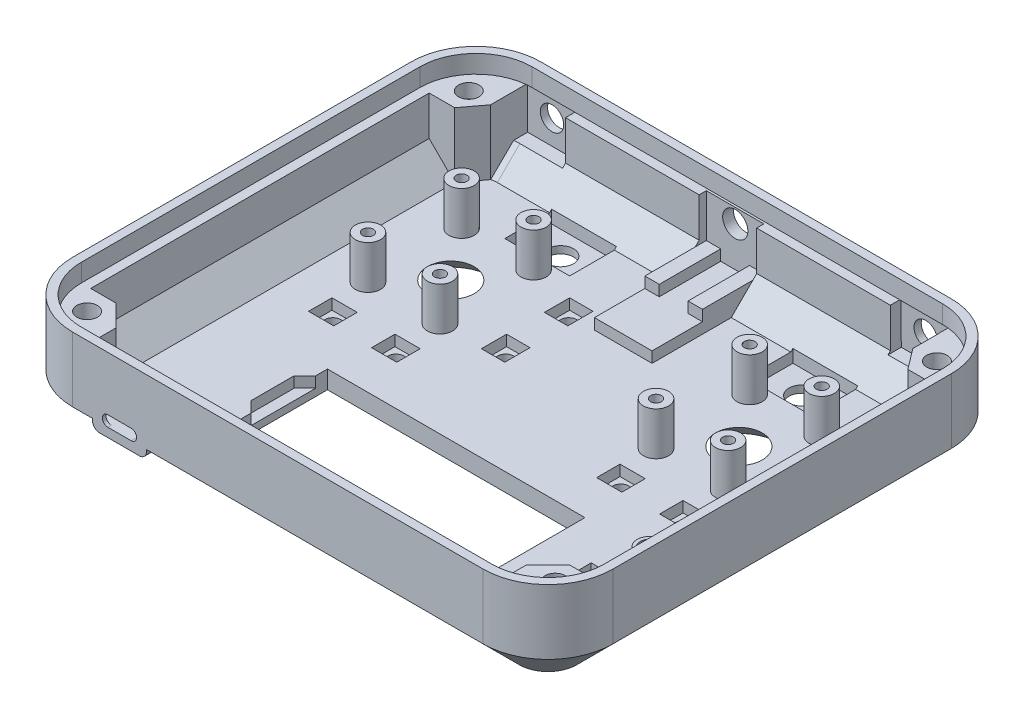
SolidWorks part; units mm, degrees
ref_plane "前视基准面" through (0, 0, 0) normal (0, 0, 1) x (1, 0, 0)
ref_plane "上视基准面" through (0, 0, 0) normal (0, 1, 0) x (1, 0, 0)
ref_plane "右视基准面" through (0, 0, 0) normal (1, 0, 0) x (0, 0, -1)
other "Configuration Table"
sketch "草图1" plane through (0, 0, 0) normal (0, 1, 0) x (1, 0, 0)
  line L1 (-57, -65) -> (57, -65)
  line L2 (-75, -47) -> (-75, 47)
  line L3 (-57, 65) -> (57, 65)
  line L4 (75, -47) -> (75, 47)
  line L5 (-75, -65) -> (75, 65) construction
  line L6 (-75, 65) -> (75, -65) construction
  arc A0 (57, -65) -> (75, -47) centre (57, -47) ccw
  arc A1 (-57, -65) -> (-75, -47) centre (-57, -47) cw
  arc A2 (-75, 47) -> (-57, 65) centre (-57, 47) cw
  arc A3 (57, 65) -> (75, 47) centre (57, 47) cw
  point P0 (0, 0)
  dimension "D3" = 18
  dimension "D1" = 150
  dimension "D2" = 130
extrude "凸台-拉伸1" add sketch "草图1" along normal blind 23
chamfer "倒角1" distance 10 angle 45 8 edges at (75, 0, 0) (69.7279, 0, -59.7279) (0, 0, -65) (-69.7279, 0, -59.7279) (-75, 0, 0) (-69.7279, 0, 59.7279) (0, 0, 65) (69.7279, 0, 59.7279)
shell "抽壳3" thickness 5 removed face at (0, 23, 0)
sketch "草图2" plane through (0, 0, -65) normal (0, 0, -1) x (-1, 0, 0)
  line L0 (0, 0) -> (0, 23) construction
  line L1 (-57, 23) -> (57, 23) construction
  circle A0 centre (0, 19) radius 3.5
  circle A1 centre (-51.8897, 18) radius 3.25
  circle A2 centre (51.8897, 18) radius 3.25
  dimension "D1" = 7
  dimension "D2" = 6.5
  dimension "D3" = 5
  dimension "D4" = 4
extrude "切除-拉伸1" cut sketch "草图2" against normal blind 27
sketch "草图3" plane through (0, 0, 0) normal (0, -1, 0) x (1, 0, 0)
  line L0 (0, 0) -> (0, -65) construction
  line L1 (57, -65) -> (-57, -65) construction
  line L2 (-57, -55) -> (57, -55) construction
  line L3 (40, -23) -> (40, 55) construction
  line L4 (57, 55) -> (-57, 55) construction
  line L5 (65, -47) -> (65, 47) construction
  line L6 (60, 25.5) -> (47.5, 25.5)
  line L7 (60, 25.5) -> (60, 45)
  line L8 (60, 45) -> (47.5, 45)
  line L9 (47.5, 25.5) -> (47.5, 45)
  line L11 (35.75, 40) -> (-35.75, 40)
  line L12 (35.75, 40) -> (35.75, 15.5)
  line L13 (35.75, 15.5) -> (-35.75, 15.5)
  line L14 (-35.75, 40) -> (-35.75, 15.5)
  line L15 (35.75, 40) -> (-35.75, 15.5) construction
  line L16 (35.75, 15.5) -> (-35.75, 40) construction
  circle A0 centre (33.5, -47) radius 3.6
  circle A1 centre (-33.5, -47) radius 3.6
  circle A2 centre (40, -23) radius 6
  circle A3 centre (-40, -23) radius 6
  circle A4 centre (48.75, 1) radius 2.25
  circle A5 centre (31.25, 1) radius 2.25
  circle A6 centre (-31.25, 1) radius 2.25
  circle A7 centre (-48.75, 1) radius 2.25
  circle A8 centre (-16, -31.75) radius 2.25
  circle A9 centre (-16, -14.25) radius 2.25
  arc A14 (-30.1535, -45.0353) -> (-30.1535, -48.9647) centre (-31.25, -47) cw [skipped]
  circle A15 centre (-48.75, -47) radius 2.25 [skipped]
  circle A16 centre (-64, -31.75) radius 2.25 [skipped]
  circle A17 centre (-64, -14.25) radius 2.25 [skipped]
  circle A18 centre (53.75, 15.5) radius 2.6
  point P38 (0, 27.75)
  point P41 (-40, -23)
  dimension "D1" = 7.2
  dimension "D2" = 67
  dimension "D3" = 8
  dimension "D5" = 80
  dimension "D6" = 12
  dimension "D7" = 4.5
  dimension "D8" = 17.5
  dimension "D9" = 24
  dimension "D15" = 5.2
  dimension "D4" = 32
  dimension "D11" = 19.5
  dimension "D12" = 12.5
  dimension "D13" = 5
  dimension "D14" = 10
  dimension "D16" = 10
  dimension "D17" = 71.5
  dimension "D18" = 24.5
  dimension "D19" = 15
  dimension "D10" = 4
extrude "切除-拉伸2" cut sketch "草图3" against normal blind 27
sketch "草图4" plane through (0, 5, 0) normal (0, 1, 0) x (1, 0, 0)
  circle A0 centre (53.75, -15.5) radius 3.5
  circle A1 centre (53.75, -15.5) radius 2.6
  dimension "D1" = 5.2
  dimension "D2" = 7
extrude "凸台-拉伸2" add sketch "草图4" along normal blind 2
sketch "草图6" plane through (0, 5, 0) normal (0, 1, 0) x (1, 0, 0)
  line L0 (0, 0) -> (0, 65) construction
  line L1 (24.5, 40.5) -> (42.5, 40.5)
  line L2 (24.5, 40.5) -> (24.5, 53.5)
  line L3 (24.5, 53.5) -> (42.5, 53.5)
  line L4 (42.5, 40.5) -> (42.5, 53.5)
  line L5 (24.5, 40.5) -> (42.5, 53.5) construction
  line L6 (24.5, 53.5) -> (42.5, 40.5) construction
  line L7 (57, 65) -> (-57, 65) construction
  line L8 (-24.5, 53.5) -> (-42.5, 53.5)
  line L9 (-42.5, 40.5) -> (-42.5, 53.5)
  line L10 (-24.5, 40.5) -> (-42.5, 40.5)
  line L11 (-24.5, 40.5) -> (-24.5, 53.5)
  point P0 (33.5, 47)
  dimension "D1" = 13
  dimension "D2" = 18
extrude "切除-拉伸3" cut sketch "草图6" against normal mid plane 6
sketch "草图7" plane through (0, 23, 0) normal (0, 1, 0) x (1, 0, 0)
  line L6 (57, 65) -> (-57, 65) construction
  line L7 (-8.0392, 52.4354) -> (7.9608, 52.4354)
  line L8 (-8.0392, 52.4354) -> (-8.0392, 62)
  line L9 (-8.0392, 62) -> (7.9608, 62)
  line L10 (7.9608, 52.4354) -> (7.9608, 62)
  line L11 (-8.0392, 52.4354) -> (7.9608, 62) construction
  line L12 (-8.0392, 62) -> (7.9608, 52.4354) construction
  point P0 (-0.0392, 57.2177)
  dimension "D1" = 16
  dimension "D2" = 3
extrude "切除-拉伸8" cut sketch "草图7" against normal blind 14
sketch "草图8" plane through (0, 0, -60) normal (0, 0, 1) x (1, 0, 0)
  line L0 (0, 0) -> (-0.0392, 23) construction
  line L1 (-58.6397, 11.25) -> (-45.1397, 11.25)
  line L2 (-58.6397, 11.25) -> (-58.6397, 24.75)
  line L3 (-58.6397, 24.75) -> (-45.1397, 24.75)
  line L4 (-45.1397, 11.25) -> (-45.1397, 24.75)
  line L5 (-58.6397, 11.25) -> (-45.1397, 24.75) construction
  line L6 (-58.6397, 24.75) -> (-45.1397, 11.25) construction
  line L7 (-57, 0) -> (57, 0) construction
  line L8 (7.9608, 23) -> (-8.0392, 23) construction
  line L9 (58.5549, 24.95) -> (45.0549, 24.9039)
  line L10 (45.101, 11.404) -> (45.0549, 24.9039)
  line L11 (58.6009, 11.4501) -> (45.101, 11.404)
  line L12 (58.6009, 11.4501) -> (58.5549, 24.95)
  point P0 (-51.8897, 18)
  dimension "D1" = 13.5
  dimension "D2" = 13.5
extrude "切除-拉伸9" cut sketch "草图8" along normal blind 13 from offset 3 offset against normal yes
sketch "草图9" plane through (0, 5, 0) normal (0, 1, 0) x (1, 0, 0)
  line L1 (-52.25, -4.25) -> (-45.25, -4.25)
  line L2 (-52.25, -4.25) -> (-52.25, 2.25)
  line L3 (-52.25, 2.25) -> (-45.25, 2.25)
  line L4 (-45.25, -4.25) -> (-45.25, 2.25)
  line L5 (-52.25, -4.25) -> (-45.25, 2.25) construction
  line L6 (-52.25, 2.25) -> (-45.25, -4.25) construction
  line L7 (-34.75, -4.25) -> (-27.75, -4.25)
  line L8 (-34.75, -4.25) -> (-34.75, 2.25)
  line L9 (-34.75, 2.25) -> (-27.75, 2.25)
  line L10 (-27.75, -4.25) -> (-27.75, 2.25)
  line L11 (-34.75, -4.25) -> (-27.75, 2.25) construction
  line L12 (-34.75, 2.25) -> (-27.75, -4.25) construction
  line L13 (0, 0) -> (0, 52.9289) construction
  line L14 (-24.5, 52.9289) -> (24.5, 52.9289) construction
  line L15 (34.75, 2.25) -> (27.75, -4.25) construction
  line L16 (34.75, -4.25) -> (27.75, 2.25) construction
  line L17 (52.25, 2.25) -> (45.25, -4.25) construction
  line L18 (52.25, -4.25) -> (45.25, 2.25) construction
  line L19 (27.75, -4.25) -> (27.75, 2.25)
  line L20 (34.75, 2.25) -> (27.75, 2.25)
  line L21 (34.75, -4.25) -> (34.75, 2.25)
  line L22 (34.75, -4.25) -> (27.75, -4.25)
  line L23 (45.25, -4.25) -> (45.25, 2.25)
  line L24 (52.25, 2.25) -> (45.25, 2.25)
  line L25 (52.25, -4.25) -> (52.25, 2.25)
  line L26 (52.25, -4.25) -> (45.25, -4.25)
  line L43 (-12.75, 10.75) -> (-19.25, 10.75)
  line L44 (-12.75, 10.75) -> (-12.75, 17.75)
  line L45 (-12.75, 17.75) -> (-19.25, 17.75)
  line L46 (-19.25, 10.75) -> (-19.25, 17.75)
  line L47 (-12.75, 28.25) -> (-19.25, 28.25)
  line L48 (-12.75, 28.25) -> (-12.75, 35.25)
  line L49 (-12.75, 35.25) -> (-19.25, 35.25)
  line L50 (-19.25, 28.25) -> (-19.25, 35.25)
  line L51 (-27.75, 50.25) -> (-27.75, 43.75) [skipped]
  line L52 (-34.75, 50.25) -> (-34.75, 43.75) [skipped]
  line L53 (-45.25, 50.25) -> (-45.25, 43.75) [skipped]
  line L54 (-52.25, 50.25) -> (-52.25, 43.75) [skipped]
  line L55 (-45.25, 43.75) -> (-52.25, 43.75) [skipped]
  line L56 (-45.25, 50.25) -> (-52.25, 50.25) [skipped]
  line L57 (-27.75, 50.25) -> (-34.75, 50.25) [skipped]
  line L58 (-27.75, 43.75) -> (-34.75, 43.75) [skipped]
  line L59 (-67.25, 35.25) -> (-60.75, 35.25) [skipped]
  line L60 (-67.25, 28.25) -> (-60.75, 28.25) [skipped]
  line L61 (-60.75, 35.25) -> (-60.75, 28.25) [skipped]
  line L62 (-67.25, 35.25) -> (-67.25, 28.25) [skipped]
  line L63 (-67.25, 17.75) -> (-60.75, 17.75) [skipped]
  line L64 (-60.75, 17.75) -> (-60.75, 10.75) [skipped]
  line L65 (-67.25, 17.75) -> (-67.25, 10.75) [skipped]
  line L66 (-67.25, 10.75) -> (-60.75, 10.75) [skipped]
  point P0 (-48.75, -1)
  point P6 (-31.25, -1)
  point P12 (-40, 23)
  point P27 (31.25, -1)
  point P28 (48.75, -1)
  point P56 (-40, 23)
  dimension "D1" = 7
  dimension "D2" = 6.5
  dimension "D3" = 7
  dimension "D4" = 6.5
  dimension "D6" = 7
  dimension "D5" = 4
extrude "切除-拉伸10" cut sketch "草图9" against normal mid plane 6
sketch "草图10" plane through (0, 5, 0) normal (0, 1, 0) x (1, 0, 0)
  line L0 (-35.75, -15.5) -> (-35.75, -40) construction
  line L1 (-32.75, -33.75) -> (-38.75, -33.75)
  line L2 (-32.75, -33.75) -> (-32.75, -21.75)
  line L3 (-32.75, -21.75) -> (-38.75, -21.75)
  line L4 (-38.75, -33.75) -> (-38.75, -21.75)
  line L5 (-32.75, -33.75) -> (-38.75, -21.75) construction
  line L6 (-32.75, -21.75) -> (-38.75, -33.75) construction
  point P0 (-35.75, -27.75)
  dimension "D1" = 12
  dimension "D2" = 6
extrude "切除-拉伸11" cut sketch "草图10" against normal mid plane 6
chamfer "倒角2" distance 3 angle 45 2 edges at (-35.75, 3.5, 33.75) (-35.75, 3.5, 21.75)
sketch "草图11" plane through (0, 0, 0) normal (0, -1, 0) x (1, 0, 0)
  circle A0 centre (40, -23) radius 6.5
  circle A1 centre (-40, -23) radius 6.5
  dimension "D1" = 13
  dimension "D2" = 13
extrude "切除-拉伸12" cut sketch "草图11" against normal blind 6
chamfer "倒角3" distance 5 angle 45 2 edges at (40, 0, -29.5) (-40, 0, -29.5)
sketch "草图12" plane through (0, 5, 0) normal (0, 1, 0) x (1, 0, 0)
  line L0 (0, 0) -> (0, 52.9289) construction
  line L1 (-24.5, 52.9289) -> (24.5, 52.9289) construction
  circle A0 centre (29, 37) radius 1.5
  circle A1 centre (29, 11) radius 1.5
  circle A2 centre (49, 11) radius 1.5
  circle A3 centre (49, 37) radius 1.5
  circle A4 centre (29, 37) radius 3.5
  circle A5 centre (49, 37) radius 3.5
  circle A6 centre (49, 11) radius 3.5
  circle A7 centre (29, 11) radius 3.5
  circle A16 centre (-31, 37) radius 1.5
  circle A17 centre (-51, 37) radius 1.5
  circle A18 centre (-51, 11) radius 1.5
  circle A19 centre (-31, 11) radius 1.5
  circle A20 centre (-31, 37) radius 3.5
  circle A21 centre (-51, 37) radius 3.5
  circle A22 centre (-51, 11) radius 3.5
  circle A23 centre (-31, 11) radius 3.5
  point P8 (40, 23)
  point P35 (-40, 23)
  dimension "D1" = 3
  dimension "D2" = 3
  dimension "D3" = 3
  dimension "D4" = 3
  dimension "D5" = 20
  dimension "D6" = 26
  dimension "D7" = 9
  dimension "D8" = 12
  dimension "D9" = 7
  dimension "D10" = 7
  dimension "D11" = 7
  dimension "D12" = 3
  dimension "D13" = 3
  dimension "D14" = 3
  dimension "D15" = 3
  dimension "D16" = 20
  dimension "D17" = 26
  dimension "D20" = 14
  dimension "D19" = 9
  dimension "D18" = 2
extrude "凸台-拉伸3" add sketch "草图12" along normal blind 12
sketch "草图13" plane through (0, 0, 60) normal (0, 0, -1) x (-1, 0, 0)
  line L0 (57, 23) -> (-57, 23) construction
  line L1 (34, 10) -> (54, 10)
  line L2 (34, 10) -> (34, 20)
  line L3 (34, 20) -> (54, 20)
  line L4 (54, 10) -> (54, 20)
  line L5 (34, 10) -> (54, 20) construction
  line L6 (34, 20) -> (54, 10) construction
  line L7 (57, 23) -> (57, 12.0711) construction
  point P0 (44, 15)
  dimension "D1" = 10
  dimension "D2" = 20
  dimension "D3" = 3
  dimension "D4" = 3
extrude "切除-拉伸13" cut sketch "草图13" against normal blind 4 contours L4 L3 L2 L1
sketch "草图14" plane through (0, 0, 64) normal (0, 0, -1) x (-1, 0, 0)
  line L0 (40.75, 11.5) -> (47.25, 11.5) construction
  line L1 (40.75, 13) -> (47.25, 13)
  line L2 (40.75, 10) -> (47.25, 10)
  line L3 (34, 10) -> (54, 10) construction
  arc A0 (40.75, 13) -> (40.75, 10) centre (40.75, 11.5) ccw
  arc A1 (47.25, 10) -> (47.25, 13) centre (47.25, 11.5) ccw
  point P2 (44, 11.5)
  point P7 (39.25, 11.5)
  point P8 (48.75, 11.5)
  point P9 (44, 10)
  dimension "D1" = 9.5
  dimension "D2" = 3
extrude "切除-拉伸14" cut sketch "草图14" against normal blind 4
sketch "草图15" plane through (0, 23, 0) normal (0, 1, 0) x (1, 0, 0)
  line L20 (72.6, -47) -> (72.6, 47)
  line L21 (-57, -62.6) -> (57, -62.6)
  line L22 (-72.6, 47) -> (-72.6, -47)
  line L23 (57, 62.6) -> (-57, 62.6)
  line L24 (72.6, -47) -> (72.6, 47)
  line L25 (-57, -62.6) -> (57, -62.6)
  line L26 (-72.6, 47) -> (-72.6, -47)
  line L27 (57, 62.6) -> (-57, 62.6)
  line L44 (75, -47) -> (75, 47)
  line L45 (-57, -65) -> (57, -65)
  line L46 (-75, 47) -> (-75, -47)
  line L47 (57, 65) -> (-57, 65)
  line L48 (75, -47) -> (75, 47)
  line L49 (-57, -65) -> (57, -65)
  line L50 (-75, 47) -> (-75, -47)
  line L51 (57, 65) -> (-57, 65)
  arc A24 (57, -62.6) -> (72.6, -47) centre (57, -47) ccw
  arc A25 (-72.6, -47) -> (-57, -62.6) centre (-57, -47) ccw
  arc A26 (-57, 62.6) -> (-72.6, 47) centre (-57, 47) ccw
  arc A27 (72.6, 47) -> (57, 62.6) centre (57, 47) ccw
  arc A28 (57, -62.6) -> (72.6, -47) centre (57, -47) ccw
  arc A29 (-72.6, -47) -> (-57, -62.6) centre (-57, -47) ccw
  arc A30 (-57, 62.6) -> (-72.6, 47) centre (-57, 47) ccw
  arc A31 (72.6, 47) -> (57, 62.6) centre (57, 47) ccw
  arc A52 (57, -65) -> (75, -47) centre (57, -47) ccw
  arc A53 (-75, -47) -> (-57, -65) centre (-57, -47) ccw
  arc A54 (-57, 65) -> (-75, 47) centre (-57, 47) ccw
  arc A55 (75, 47) -> (57, 65) centre (57, 47) ccw
  arc A56 (57, -65) -> (75, -47) centre (57, -47) ccw
  arc A57 (-75, -47) -> (-57, -65) centre (-57, -47) ccw
  arc A58 (-57, 65) -> (-75, 47) centre (-57, 47) ccw
  arc A59 (75, 47) -> (57, 65) centre (57, 47) ccw
  dimension "D4" = 18
  dimension "D3" = 150
  dimension "D5" = 130
  dimension "D6" = 145.2
  dimension "D1" = 2.4
  dimension "D2" = 0
extrude "凸台-拉伸4" add sketch "草图15" along normal blind 5
sketch "草图26" plane through (0, 0, 0) normal (0, -1, 0) x (1, 0, 0)
  text T0 "<b>              PTSFDTZ</b>" font "@Adobe Gothic Std B" height 10
extrude "切除-拉伸16" cut sketch "草图26" against normal blind 1
sketch "草图27" plane through (0, 23, 0) normal (0, 1, 0) x (1, 0, 0)
  line L0 (70, -47) -> (62.9289, -47)
  line L1 (58.5988, 52.7076) -> (62.9289, 47)
  line L2 (57, -52.9289) -> (57, -60)
  line L3 (58.5988, 59.9013) -> (58.5988, 52.7076)
  line L4 (70, 47) -> (62.9289, 47)
  line L5 (-58.6397, 59.8962) -> (-58.6397, 52.6977)
  line L6 (-70, 47) -> (-62.9289, 47)
  line L7 (-70, -47) -> (-62.9289, -47)
  line L8 (-62.9289, -47) -> (-57, -52.9289)
  line L9 (-57, -52.9289) -> (-57, -60)
  line L10 (62.9289, -47) -> (57, -52.9289)
  line L11 (-58.6397, 52.6977) -> (-62.9289, 47)
  arc A0 (-70, -47) -> (-57, -60) centre (-57, -47) ccw
  arc A2 (-58.6397, 59.8962) -> (-70, 47) centre (-57, 47) ccw
  arc A4 (70, 47) -> (58.5988, 59.9013) centre (57, 47) ccw
  arc A6 (57, -60) -> (70, -47) centre (57, -47) ccw
extrude "凸台-拉伸5" add sketch "草图27" against normal up to next
sketch "草图28" plane through (0, 23, 0) normal (0, 1, 0) x (1, 0, 0)
  line L0 (57, 65) -> (-57, 65) construction
  line L1 (75, -47) -> (75, 47) construction
  line L2 (0, 0) -> (0, 65) construction
  line L3 (0, 0) -> (75, 0) construction
  line L4 (-57, -65) -> (57, -65) construction
  circle A0 centre (65, 53) radius 2.85
  circle A1 centre (-65, 53) radius 2.85
  circle A2 centre (-65, -53) radius 2.85
  circle A3 centre (65, -53) radius 2.85
  dimension "D1" = 5.7
  dimension "D3" = 10
  dimension "D2" = 12
  dimension "D4" = 12
extrude "切除-拉伸17" cut sketch "草图28" against normal blind 4
sketch "草图29" plane through (0, 5, 0) normal (0, 1, 0) x (1, 0, 0)
  line L1 (-8.0392, 56.9289) -> (7.9608, 56.9289)
  line L2 (-8.0392, 56.9289) -> (-8.0392, 30.9289)
  line L3 (-8.0392, 30.9289) -> (7.9608, 30.9289)
  line L4 (7.9608, 56.9289) -> (7.9608, 30.9289)
  dimension "D1" = 16
  dimension "D2" = 26
extrude "凸台-拉伸6" add sketch "草图29" along normal blind 6
sketch "草图30" plane through (0, 9, 0) normal (0, 1, 0) x (1, 0, 0)
  line L1 (-8.0392, 62) -> (7.9608, 62)
  line L2 (-8.0392, 62) -> (-8.0392, 56.9289)
  line L3 (-8.0392, 56.9289) -> (7.9608, 56.9289)
  line L4 (7.9608, 62) -> (7.9608, 56.9289)
extrude "凸台-拉伸7" add sketch "草图30" along normal blind 2
sketch "草图31" plane through (0, 11, 0) normal (0, 1, 0) x (1, 0, 0)
  line L0 (7.9608, 62) -> (-8.0392, 62) construction
  line L1 (-4.0392, 62) -> (3.9608, 62)
  line L2 (-4.0392, 62) -> (-4.0392, 44.9289)
  line L3 (-4.0392, 30.9289) -> (3.9608, 30.9289)
  line L4 (3.9608, 62) -> (3.9608, 44.9289)
  line L5 (-8.0392, 30.9289) -> (7.9608, 30.9289) construction
  line L6 (-8.0392, 52.9289) -> (-8.0392, 58.9289) construction
  line L7 (-8.0392, 58.9289) -> (-8.0392, 30.9289) construction
  line L8 (-8.0392, 44.9289) -> (-4.0392, 44.9289)
  line L9 (-8.0392, 44.9289) -> (-8.0392, 30.9289)
  line L10 (-8.0392, 30.9289) -> (7.9608, 30.9289)
  line L11 (7.9608, 44.9289) -> (7.9608, 30.9289)
  line L12 (3.9608, 44.9289) -> (7.9608, 44.9289)
  point P8 (-0.0392, 62)
  line M5 (-8.0392, 58.9289) -> (-8.0392, 30.9289)
  line M6 (-8.0392, 30.9289) -> (7.9608, 30.9289)
  line M7 (7.9608, 30.9289) -> (7.9608, 58.9289)
  line M9 (7.9608, 62) -> (-8.0392, 62)
  dimension "D1" = 8
  dimension "D2" = 4
extrude "切除-拉伸19" cut sketch "草图31" against normal blind 3 contours L12 L4 L2 L8 M9 M5 M6 M7 region at (-0.0392, 11, -43.8132)
sketch "草图32" plane through (0, 0, 64) normal (0, 0, -1) x (-1, 0, 0)
  line L0 (54, 10) -> (54, 20) construction
  line L1 (34, 20) -> (54, 20)
  line L2 (34, 20) -> (34, 10)
  line L3 (34, 10) -> (54, 10)
  line L4 (54, 20) -> (54, 10)
extrude "切除-拉伸20" cut sketch "草图32" along normal blind 9
sketch "草图33" plane through (0, 10, 0) normal (0, 1, 0) x (1, 0, 0)
  line L1 (-54, -57.9289) -> (-34, -57.9289)
  line L2 (-54, -57.9289) -> (-54, -48.9289)
  line L3 (-54, -48.9289) -> (-34, -48.9289)
  line L4 (-34, -57.9289) -> (-34, -48.9289)
  dimension "D1" = 20
  dimension "D2" = 9
extrude "凸台-拉伸8" add sketch "草图33" against normal blind 6
sketch "草图35" plane through (0, 10, 0) normal (0, 1, 0) x (1, 0, 0)
  line L6 (-57, -65) -> (57, -65) construction
  line L7 (-51.5, -54.9331) -> (-36.5, -54.9331)
  line L8 (-51.5, -54.9331) -> (-51.5, -65)
  line L9 (-51.5, -65) -> (-36.5, -65)
  line L10 (-36.5, -54.9331) -> (-36.5, -65)
  line L11 (-34, -48.9289) -> (-54, -48.9289) construction
  point P6 (-44, -48.9289)
  point P7 (-44, -54.9331)
  dimension "D1" = 15
extrude "凸台-拉伸10" add sketch "草图35" against normal blind 2.5
fillet "圆角3" radius 2 2 edges at (-36.5, 7.5, 63.75) (-51.5, 7.5, 63.75)
equation "\"4‘\"=3"
equation "\"198、\"=17"
